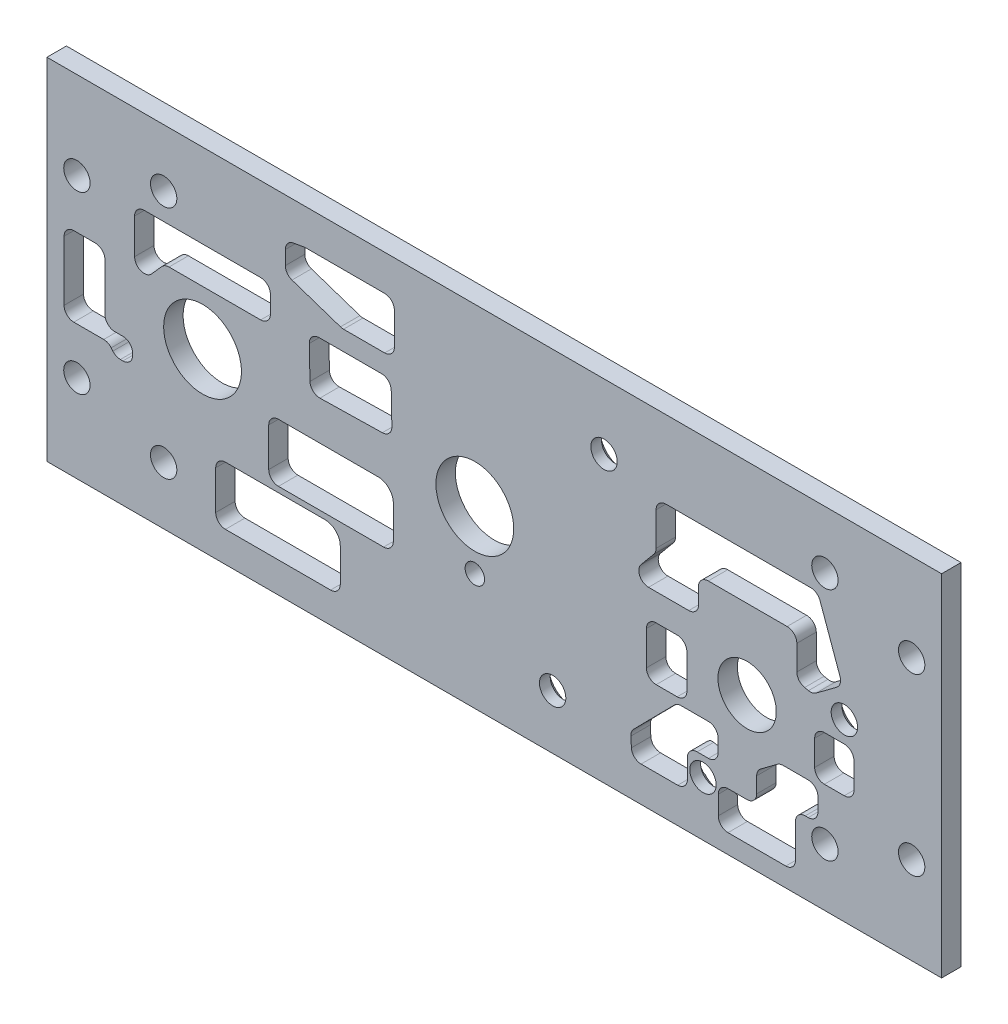
SolidWorks part; units mm, degrees
ref_plane "Front Plane" through (0, 0, 0) normal (0, 0, 1) x (1, 0, 0)
ref_plane "Top Plane" through (0, 0, 0) normal (0, 1, 0) x (1, 0, 0)
ref_plane "Right Plane" through (0, 0, 0) normal (1, 0, 0) x (0, 0, -1)
sketch "Sketch1" plane through (0, 0, 0) normal (0, 0, 1) x (1, 0, 0)
  line L4 (0, 57.15) -> (-146.05, 57.15)
  line L5 (-146.05, 57.15) -> (-146.05, 0)
  line L6 (-146.05, 0) -> (0, 0)
  line L7 (0, 0) -> (0, 57.15)
  line L8 (0, 57.15) -> (-146.05, 57.15)
  line L9 (-146.05, 57.15) -> (-146.05, 0)
  line L10 (-146.05, 0) -> (0, 0)
  line L11 (0, 0) -> (0, 57.15)
  dimension "D1" = 0
extrude "Boss-Extrude1" add sketch "Sketch1" against normal blind 3.175
hole_wizard "#6 Clearance Hole1" positions "Sketch3" profile "Sketch2" hole size "#6" standard "ANSI Inch" end condition through all
sketch "Sketch3" plane through (0, 0, -3.175) normal (0, 0, -1) x (-1, 0, 0)
  point P0 (4.8895, 42.8625)
  point P3 (141.1605, 42.8625)
  point P6 (141.1605, 14.2875)
  point P9 (4.8895, 14.2875)
  point P12 (19.05, 47.752)
  point P15 (19.05, 9.398)
  point P18 (127, 9.398)
  point P21 (127, 47.752)
sketch "Sketch2" plane through (-4.8895, 42.8625, -3.175) normal (1, 0, 0) x (0, 1, 0)
  line L0 (0, 0) -> (0, 3.175)
  line L1 (0, 3.175) -> (2.1526, 3.175)
  line L2 (2.1526, 3.175) -> (2.1526, 0)
  line L5 (2.1526, 0) -> (0, 0)
  line L11 (0, -6.35) -> (0, 107.95) construction
  dimension "Thru Hole Dia." = 4.3053
  dimension "Thru Hole Depth" = 3.175
hole_wizard "1/2 (0.5) Diameter Hole1" positions "Sketch5" profile "Sketch4" hole size "1/2" standard "ANSI Inch" end condition through all
sketch "Sketch5" plane through (0, 0, -3.175) normal (0, 0, -1) x (-1, 0, 0)
  point P0 (76.2, 28.575)
  point P3 (120.65, 28.575)
sketch "Sketch4" plane through (-76.2, 28.575, -3.175) normal (1, 0, 0) x (0, 1, 0)
  line L0 (0, 0) -> (0, 3.175)
  line L1 (0, 3.175) -> (6.35, 3.175)
  line L2 (6.35, 3.175) -> (6.35, 0)
  line L5 (6.35, 0) -> (0, 0)
  line L11 (0, -6.35) -> (0, 107.95) construction
  dimension "Thru Hole Dia." = 12.7
  dimension "Thru Hole Depth" = 3.175
hole_wizard "3/8 (0.375) Diameter Hole1" positions "Sketch7" profile "Sketch6" hole size "3/8" standard "ANSI Inch" end condition through all
sketch "Sketch7" plane through (0, 0, -3.175) normal (0, 0, -1) x (-1, 0, 0)
  point P0 (31.75, 24.13)
sketch "Sketch6" plane through (-31.75, 24.13, -3.175) normal (1, 0, 0) x (0, 1, 0)
  line L0 (0, 0) -> (0, 3.175)
  line L1 (0, 3.175) -> (4.7625, 3.175)
  line L2 (4.7625, 3.175) -> (4.7625, 0)
  line L5 (4.7625, 0) -> (0, 0)
  line L11 (0, -6.35) -> (0, 107.95) construction
  dimension "Thru Hole Dia." = 9.525
  dimension "Thru Hole Depth" = 3.175
hole_wizard "1/8 (0.125) Diameter Hole1" positions "Sketch9" profile "Sketch8" hole size "1/8" standard "ANSI Inch" end condition through all
sketch "Sketch9" plane through (0, 0, -3.175) normal (0, 0, -1) x (-1, 0, 0)
  point P0 (76.2, 19.05)
sketch "Sketch8" plane through (-76.2, 19.05, -3.175) normal (1, 0, 0) x (0, 1, 0)
  line L0 (0, 0) -> (0, 3.175)
  line L1 (0, 3.175) -> (1.5875, 3.175)
  line L2 (1.5875, 3.175) -> (1.5875, 0)
  line L5 (1.5875, 0) -> (0, 0)
  line L11 (0, -6.35) -> (0, 107.95) construction
  dimension "Thru Hole Dia." = 3.175
  dimension "Thru Hole Depth" = 3.175
hole_wizard "CSK for #6 Flat Head Machine Screw (100)2" positions "Sketch13" profile "Sketch14" countersink size "#6" standard "ANSI Inch" end condition through all
sketch "Sketch13" plane through (0, 0, -3.175) normal (0, 0, -1) x (-1, 0, 0)
  point P0 (63.5, 8.89)
  point P2 (55.108, 46.4933)
  point P4 (15.875, 28.58)
  point P6 (38.95, 8.89)
sketch "Sketch14" plane through (-63.5, 8.89, -3.175) normal (1, 0, 0) x (0, 1, 0)
  line L0 (0, 0) -> (0, 3.175)
  line L1 (0, 3.175) -> (2.1526, 3.175)
  line L2 (2.1526, 3.175) -> (2.1526, 1.4209)
  line L3 (2.1526, 1.4209) -> (3.846, 0)
  line L5 (3.846, 0) -> (0, 0)
  line L6 (-2.1526, 1.4209) -> (-3.846, 0) construction
  line L11 (0, -6.35) -> (0, 107.95) construction
  dimension "Thru Hole Dia." = 4.3053
  dimension "Thru Hole Depth" = 3.175
  dimension "Near C'Sink Dia." = 7.692
  dimension "Near C'Sink Angle" = 100
sketch "Sketch15" plane through (0, 0, -3.175) normal (0, 0, -1) x (-1, 0, 0)
  line L0 (21.3472, 44.4967) -> (45.0121, 44.4967)
  line L1 (46.5996, 42.9092) -> (46.5996, 37.4558)
  line L2 (46.9673, 36.4398) -> (49.0674, 33.9182)
  line L3 (47.8475, 31.3147) -> (41.2725, 31.3147)
  line L4 (39.685, 32.9022) -> (39.685, 35.5002)
  line L5 (38.0975, 37.0877) -> (25.2199, 37.0877)
  line L6 (23.6324, 35.5002) -> (23.6324, 31.4465)
  line L7 (22.3581, 29.8902) -> (21.7351, 29.7648)
  line L8 (20.4716, 30.0495) -> (17.1327, 32.5446)
  line L9 (16.5889, 34.3526) -> (19.853, 43.4456)
  line L10 (43.1694, 26.9041) -> (46.5996, 26.9041)
  line L11 (48.1871, 25.3166) -> (48.1871, 19.7591)
  line L12 (46.5996, 18.1716) -> (43.1694, 18.1716)
  line L13 (41.5819, 19.7591) -> (41.5819, 25.3166)
  line L14 (90.921, 42.9092) -> (97.6271, 42.9092)
  line L15 (98.1323, 42.9918) -> (106.0507, 45.6499)
  line L16 (107.133, 47.1549) -> (107.133, 49.4288)
  line L17 (105.8312, 50.9904) -> (104.1288, 51.3019)
  line L18 (103.8431, 51.3278) -> (90.921, 51.3278)
  line L19 (89.3335, 49.7403) -> (89.3335, 44.4967)
  line L20 (103.2202, 38.1053) -> (103.1126, 32.7901)
  line L21 (101.4933, 31.235) -> (91.2976, 31.4416)
  line L22 (89.7426, 33.0609) -> (89.8461, 38.1696)
  line L23 (91.4333, 39.725) -> (101.6331, 39.725)
  line L24 (111.1606, 37.4558) -> (126.1275, 37.4558)
  line L25 (127.3155, 36.9213) -> (128.968, 35.057)
  line L26 (131.7435, 36.11) -> (131.7435, 41.8581)
  line L27 (130.156, 43.4456) -> (111.1606, 43.4456)
  line L28 (109.5731, 41.8581) -> (109.5731, 39.0433)
  line L29 (143.2554, 33.2422) -> (143.2554, 23.4739)
  line L30 (141.6679, 21.8864) -> (136.7791, 21.8864)
  line L31 (135.5587, 21.3143) -> (135.2847, 20.9849)
  line L32 (134.0643, 20.4128) -> (133.6479, 20.4128)
  line L33 (132.0604, 22.0003) -> (132.0604, 22.3105)
  line L34 (133.6479, 23.898) -> (134.9896, 23.898)
  line L35 (136.5771, 25.4855) -> (136.5771, 33.2422)
  line L36 (138.1646, 34.8297) -> (141.6679, 34.8297)
  line L37 (91.9714, 24.8598) -> (108.2562, 24.8598)
  line L40 (108.2562, 15.3802) -> (91.0931, 15.3802)
  line L41 (89.5056, 16.9677) -> (89.5056, 22.394)
  line L42 (15.8936, 25.1311) -> (19.134, 25.1311)
  line L43 (20.7215, 23.5436) -> (20.7215, 19.4102)
  line L44 (19.134, 17.8227) -> (15.8936, 17.8227)
  line L45 (14.3061, 19.4102) -> (14.3061, 23.5436)
  line L46 (20.1879, 15.5305) -> (20.1879, 13.3812)
  line L47 (21.7754, 11.7937) -> (22.2638, 11.7937)
  line L48 (23.8513, 10.2062) -> (23.8513, 4.7003)
  line L49 (25.4388, 3.1128) -> (34.8743, 3.1128)
  line L50 (36.4618, 4.7003) -> (36.4618, 7.7524)
  line L52 (25.8742, 17.118) -> (21.7754, 17.118)
  line L53 (36.4835, 15.651) -> (36.4835, 13.6067)
  line L54 (38.071, 12.0192) -> (39.9092, 12.0192)
  line L55 (41.4967, 10.4317) -> (41.4967, 7.3058)
  line L56 (43.0842, 5.7183) -> (49.0555, 5.7183)
  line L57 (50.6408, 7.2234) -> (50.725, 8.8432)
  line L58 (50.2698, 10.0404) -> (43.6356, 16.7658)
  line L59 (42.5054, 17.2385) -> (38.071, 17.2385)
  line L60 (26.825, 16.8018) -> (29.5567, 14.759)
  line L61 (30.1935, 13.4877) -> (30.1935, 10.9274)
  line L62 (31.781, 9.3399) -> (34.8743, 9.3399)
  line L63 (109.8437, 23.2723) -> (109.8437, 16.9677)
  line L64 (100.6444, 14.4687) -> (116.9139, 14.4687)
  line L65 (116.9139, 4.9739) -> (99.7509, 4.9739)
  line L66 (98.1634, 6.5614) -> (98.1634, 11.9877)
  line L67 (118.5014, 12.8812) -> (118.5014, 6.5614)
  arc A0 (17.1327, 32.5446) -> (16.5889, 34.3526) centre (18.083, 33.8163) cw
  arc A1 (21.3472, 44.4967) -> (19.853, 43.4456) centre (21.3472, 42.9092) ccw
  arc A2 (45.0121, 44.4967) -> (46.5996, 42.9092) centre (45.0121, 42.9092) cw
  arc A3 (46.5996, 37.4558) -> (46.9673, 36.4398) centre (48.1871, 37.4558) ccw
  arc A4 (49.0674, 33.9182) -> (47.8475, 31.3147) centre (47.8475, 32.9022) cw
  arc A5 (41.2725, 31.3147) -> (39.685, 32.9022) centre (41.2725, 32.9022) cw
  arc A6 (39.685, 35.5002) -> (38.0975, 37.0877) centre (38.0975, 35.5002) ccw
  arc A7 (25.2199, 37.0877) -> (23.6324, 35.5002) centre (25.2199, 35.5002) ccw
  arc A8 (23.6324, 31.4465) -> (22.3581, 29.8902) centre (22.0449, 31.4465) cw
  arc A9 (21.7351, 29.7648) -> (20.4716, 30.0495) centre (21.4219, 31.3211) cw
  arc A10 (43.1694, 26.9041) -> (41.5819, 25.3166) centre (43.1694, 25.3166) ccw
  arc A11 (46.5996, 26.9041) -> (48.1871, 25.3166) centre (46.5996, 25.3166) cw
  arc A12 (48.1871, 19.7591) -> (46.5996, 18.1716) centre (46.5996, 19.7591) cw
  arc A13 (43.1694, 18.1716) -> (41.5819, 19.7591) centre (43.1694, 19.7591) cw
  arc A14 (104.1288, 51.3019) -> (103.8431, 51.3278) centre (103.8431, 49.7403) ccw
  arc A15 (107.133, 49.4288) -> (105.8312, 50.9904) centre (105.5455, 49.4288) ccw
  arc A16 (106.0507, 45.6499) -> (107.133, 47.1549) centre (105.5455, 47.1549) ccw
  arc A17 (97.6271, 42.9092) -> (98.1323, 42.9918) centre (97.6271, 44.4967) ccw
  arc A18 (90.921, 51.3278) -> (89.3335, 49.7403) centre (90.921, 49.7403) ccw
  arc A19 (90.921, 42.9092) -> (89.3335, 44.4967) centre (90.921, 44.4967) cw
  arc A20 (89.8461, 38.1696) -> (91.4333, 39.725) centre (91.4333, 38.1375) cw
  arc A21 (91.2976, 31.4416) -> (89.7426, 33.0609) centre (91.3298, 33.0287) cw
  arc A22 (103.1126, 32.7901) -> (101.4933, 31.235) centre (101.5254, 32.8222) cw
  arc A23 (103.2202, 38.1053) -> (101.6331, 39.725) centre (101.6331, 38.1375) ccw
  arc A24 (131.7435, 41.8581) -> (130.156, 43.4456) centre (130.156, 41.8581) ccw
  arc A25 (128.968, 35.057) -> (131.7435, 36.11) centre (130.156, 36.11) ccw
  arc A26 (126.1275, 37.4558) -> (127.3155, 36.9213) centre (126.1275, 35.8683) cw
  arc A27 (111.1606, 37.4558) -> (109.5731, 39.0433) centre (111.1606, 39.0433) cw
  arc A28 (111.1606, 43.4456) -> (109.5731, 41.8581) centre (111.1606, 41.8581) ccw
  arc A29 (143.2554, 23.4739) -> (141.6679, 21.8864) centre (141.6679, 23.4739) cw
  arc A30 (136.7791, 21.8864) -> (135.5587, 21.3143) centre (136.7791, 20.2989) ccw
  arc A31 (135.2847, 20.9849) -> (134.0643, 20.4128) centre (134.0643, 22.0003) cw
  arc A32 (133.6479, 20.4128) -> (132.0604, 22.0003) centre (133.6479, 22.0003) cw
  arc A33 (132.0604, 22.3105) -> (133.6479, 23.898) centre (133.6479, 22.3105) cw
  arc A34 (134.9896, 23.898) -> (136.5771, 25.4855) centre (134.9896, 25.4855) ccw
  arc A35 (136.5771, 33.2422) -> (138.1646, 34.8297) centre (138.1646, 33.2422) cw
  arc A36 (143.2554, 33.2422) -> (141.6679, 34.8297) centre (141.6679, 33.2422) ccw
  arc A37 (91.0931, 15.3802) -> (89.5056, 16.9677) centre (91.0931, 16.9677) cw
  arc A41 (91.9714, 24.8598) -> (89.5056, 22.394) centre (91.9714, 22.394) ccw
  arc A42 (15.8936, 17.8227) -> (14.3061, 19.4102) centre (15.8936, 19.4102) cw
  arc A43 (20.7215, 19.4102) -> (19.134, 17.8227) centre (19.134, 19.4102) cw
  arc A44 (19.134, 25.1311) -> (20.7215, 23.5436) centre (19.134, 23.5436) cw
  arc A45 (15.8936, 25.1311) -> (14.3061, 23.5436) centre (15.8936, 23.5436) ccw
  arc A47 (34.8743, 3.1128) -> (36.4618, 4.7003) centre (34.8743, 4.7003) ccw
  arc A48 (23.8513, 4.7003) -> (25.4388, 3.1128) centre (25.4388, 4.7003) ccw
  arc A49 (20.1879, 13.3812) -> (21.7754, 11.7937) centre (21.7754, 13.3812) ccw
  arc A51 (20.1879, 15.5305) -> (21.7754, 17.118) centre (21.7754, 15.5305) cw
  arc A52 (22.2638, 11.7937) -> (23.8513, 10.2062) centre (22.2638, 10.2062) cw
  arc A53 (25.8742, 17.118) -> (26.825, 16.8018) centre (25.8742, 15.5305) cw
  arc A54 (50.725, 8.8432) -> (50.2698, 10.0404) centre (49.1397, 8.9256) ccw
  arc A55 (49.0555, 5.7183) -> (50.6408, 7.2234) centre (49.0555, 7.3058) ccw
  arc A56 (41.4967, 7.3058) -> (43.0842, 5.7183) centre (43.0842, 7.3058) ccw
  arc A57 (39.9092, 12.0192) -> (41.4967, 10.4317) centre (39.9092, 10.4317) cw
  arc A58 (36.4835, 13.6067) -> (38.071, 12.0192) centre (38.071, 13.6067) ccw
  arc A59 (43.6356, 16.7658) -> (42.5054, 17.2385) centre (42.5054, 15.651) ccw
  arc A60 (36.4835, 15.651) -> (38.071, 17.2385) centre (38.071, 15.651) cw
  arc A61 (29.5567, 14.759) -> (30.1935, 13.4877) centre (28.606, 13.4877) cw
  arc A62 (30.1935, 10.9274) -> (31.781, 9.3399) centre (31.781, 10.9274) ccw
  arc A63 (36.4618, 7.7524) -> (34.8743, 9.3399) centre (34.8743, 7.7524) ccw
  arc A64 (109.8437, 16.9677) -> (108.2562, 15.3802) centre (108.2562, 16.9677) cw
  arc A65 (108.2562, 24.8598) -> (109.8437, 23.2723) centre (108.2562, 23.2723) cw
  arc A66 (99.7509, 4.9739) -> (98.1634, 6.5614) centre (99.7509, 6.5614) cw
  arc A67 (100.6444, 14.4687) -> (98.1634, 11.9877) centre (100.6444, 11.9877) ccw
  arc A68 (118.5014, 6.5614) -> (116.9139, 4.9739) centre (116.9139, 6.5614) cw
  arc A69 (116.9139, 14.4687) -> (118.5014, 12.8812) centre (116.9139, 12.8812) cw
  dimension "D1" = 1.5875
  dimension "D2" = 1.5875
  dimension "D3" = 1.5875
  dimension "D4" = 1.5875
  dimension "D5" = 1.5875
  dimension "D6" = 1.5875
  dimension "D7" = 1.5875
  dimension "D8" = 1.5875
  dimension "D9" = 1.5875
  dimension "D10" = 1.5875
  dimension "D11" = 1.5875
  dimension "D12" = 1.5875
  dimension "D13" = 1.5875
extrude "Cut-Extrude1" cut sketch "Sketch15" against normal through all
